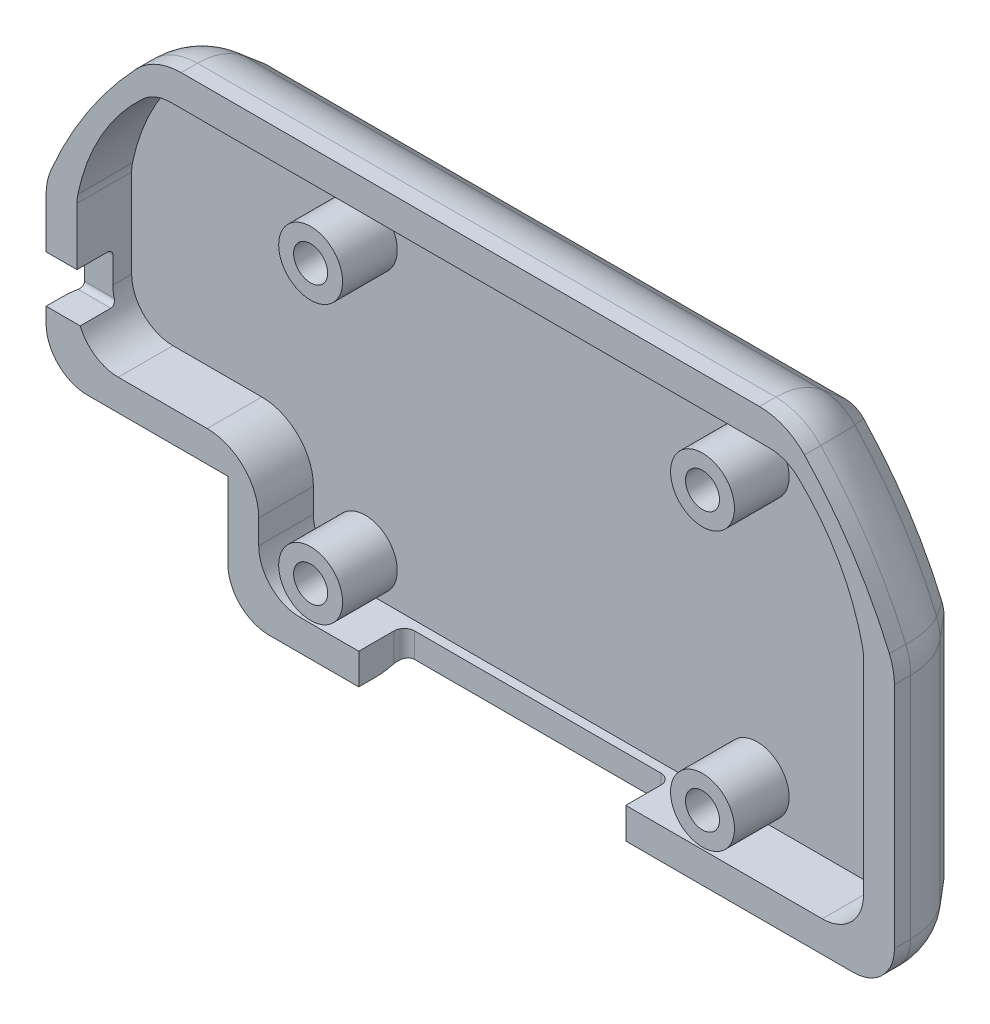
SolidWorks part; units mm, degrees
ref_plane "Alzado" through (0, 0, 0) normal (0, 0, 1) x (1, 0, 0)
ref_plane "Planta" through (0, 0, 0) normal (0, 1, 0) x (1, 0, 0)
ref_plane "Vista lateral" through (0, 0, 0) normal (1, 0, 0) x (0, 0, -1)
sketch "Croquis2" plane through (0, 0, 0) normal (0, 0, 1) x (1, 0, 0)
  line L0 (-43.6, 25.3285) -> (-43.6, 41.313)
  line L1 (-32.9688, 56.9561) -> (28.051, 56.9561)
  line L2 (38.6624, 41.313) -> (38.6624, 25.3285)
  line L7 (-43.6, 25.3285) -> (-25.98, 25.3285)
  line L8 (-25.98, 25.3285) -> (-25.98, 13.9787)
  line L9 (-25.98, 13.9787) -> (38.6624, 13.9787)
  line L10 (38.6624, 13.9787) -> (38.6624, 25.3285)
  arc A0 (-43.6, 41.313) -> (-32.9688, 56.9561) centre (-3.7394, 25.6575) cw
  arc A1 (28.051, 56.9561) -> (38.6624, 41.313) centre (-1.2097, 25.6867) cw
extrude "Saliente-Extruir1" add sketch "Croquis2" along normal blind 8.3
sketch "Croquis3" plane through (0, 0, 8.3) normal (0, 0, 1) x (1, 0, 0)
  line L0 (35.6624, 41.313) -> (35.6624, 28.3285)
  line L1 (-40.6, 28.3285) -> (-22.98, 28.3285)
  line L2 (-40.6, 41.313) -> (-40.6, 28.3285)
  line L7 (-22.98, 28.3285) -> (-22.98, 16.9787)
  line L8 (-22.98, 16.9787) -> (35.6624, 16.9787)
  line L11 (35.6624, 16.9787) -> (35.6624, 28.3285)
  line L17 (-32.9688, 53.9561) -> (28.0724, 53.9561)
  arc A0 (-40.6, 41.313) -> (-32.9688, 53.9561) centre (-19.994, 37.5001) cw
  arc A1 (28.0724, 53.9561) -> (35.6624, 41.313) centre (14.5103, 37.2147) cw
extrude "Cortar-Extruir1" cut sketch "Croquis3" against normal blind 5.3
fillet "Redondeo1" radius 4 10 edges at (35.6624, 16.9787, 5.65) (35.6624, 41.313, 5.65) (28.0724, 53.9561, 5.65) (-22.98, 16.9787, 5.65) (-40.6, 28.3285, 5.65) (-32.9688, 53.9561, 5.65) (-40.6, 41.313, 5.65) (38.6624, 13.9787, 4.15) (-25.98, 13.9787, 4.15) (-43.6, 25.3285, 4.15)
fillet "Redondeo2" radius 6 4 edges at (-43.6, 41.313, 4.15) (-32.9688, 56.9561, 4.15) (38.6624, 41.313, 4.15) (28.051, 56.9561, 4.15)
chamfer "Chaflán1" distance 3.5 angle 50 15 edges at (27.9535, 56.4654, 0) (-2.4607, 56.9561, 0) (-32.872, 56.4667, 0) (-39.5452, 49.1503, 0) (-43.478, 41.3361, 0) (-43.6, 34.7305, 0) (-42.4285, 26.5001, 0) (-32.79, 25.3285, 0) (-25.98, 21.6536, 0) (-24.8085, 15.1503, 0) (6.3412, 13.9787, 0) (37.4908, 15.1503, 0) (38.6624, 29.0568, 0) (38.5409, 41.3362, 0) (34.6182, 49.1458, 0) first distance on face at (-6.9571, 35.4937, 0)
fillet "Redondeo3" radius 7 15 edges at (-42.4285, 26.5001, 4.1711) (-24.8085, 15.1503, 4.1711) (-32.79, 25.3285, 4.1711) (-25.98, 21.6536, 4.1711) (-43.6, 34.7305, 4.1711) (-43.478, 41.3361, 4.1711) (-39.5452, 49.1503, 4.1711) (-32.872, 56.4667, 4.1711) (27.9535, 56.4654, 4.1711) (-2.4607, 56.9561, 4.1711) (38.5409, 41.3362, 4.1711) (34.6182, 49.1458, 4.1711) (38.6624, 29.0568, 4.1711) (37.4908, 15.1503, 4.1711) (6.3412, 13.9787, 4.1711)
sketch "Croquis4" plane through (0, 0, 0) normal (0, 0, -1) x (-1, 0, 0)
  circle A8 centre (-20.0535, 20.2867) radius 2.775
  circle A10 centre (-20.0535, 47.1867) radius 2.775
  circle A11 centre (17.9465, 47.2217) radius 2.775
  circle A12 centre (17.9465, 20.3217) radius 2.755
  dimension "D2" = 26.9
extrude "Cortar-Extruir2" cut sketch "Croquis4" against normal blind 5
sketch "Croquis7" plane through (-23.5317, 0, -19.7454) normal (-0.766, 0, -0.6428) x (-0.6428, 0, 0.766)
sketch "Croquis8" plane through (-43.6, 0, 0) normal (-1, 0, 0) x (0, 0, 1)
  line L0 (8.6236, 35.3575) -> (8.6236, 30.7915)
  line L4 (4.8292, 35.3575) -> (4.8292, 30.7915)
  line L5 (4.8292, 30.7915) -> (8.6236, 30.7915)
  line L6 (8.6236, 35.3575) -> (4.8292, 35.3575)
extrude "Cortar-Extruir3" cut sketch "Croquis8" against normal blind 5
sketch "Croquis9" plane through (-25.98, 0, 0) normal (-1, 0, 0) x (0, 0, 1)
  line L0 (8.4088, 23.1178) -> (8.4088, 17.9733)
  line L1 (8.4088, 23.1178) -> (4.7271, 23.1178)
  line L2 (4.7271, 23.1178) -> (4.7935, 18.0212)
  line L3 (4.7935, 18.0212) -> (8.4088, 17.9733)
fillet "Redondeo8" radius 5 1 edges at (-22.98, 28.3285, 5.65)
sketch "Croquis12" plane through (0, 0, 3) normal (0, 0, 1) x (1, 0, 0)
  circle A1 centre (-17.9465, 47.2217) radius 3.1
  circle A2 centre (-17.9465, 47.2217) radius 1.65
  circle A3 centre (-17.9465, 20.3217) radius 1.65
  circle A4 centre (-17.9465, 20.3217) radius 3.1
  circle A5 centre (20.0535, 20.2867) radius 1.65
  circle A6 centre (20.0535, 20.2867) radius 3.1
  circle A7 centre (20.0535, 47.1867) radius 1.65
  circle A8 centre (20.0535, 47.1867) radius 3.1
  circle A10 centre (20.0535, 20.2867) radius 2.775 construction
  circle A11 centre (20.0535, 47.1867) radius 2.775 construction
  circle A14 centre (-17.9465, 47.2217) radius 2.775 construction
  circle A15 centre (-17.9465, 20.3217) radius 2.755 construction
extrude "Saliente-Extruir4" add sketch "Croquis12" along normal up to surface (5.3 mm away) up to face at (-10.4031, 35.2913, 8.3)
fillet "Redondeo9" radius 0.5 2 edges at (-41.8165, 30.7915, 4.8292) (-41.9701, 35.3575, 4.8292)
sketch "Croquis14" plane through (0, 16.9787, 0) normal (0, 1, 0) x (1, 0, 0)
  line L1 (-13.279, -9.379) -> (-13.2784, -3.8865)
  line L2 (-13.2784, -3.8865) -> (12.6103, -3.8865)
  line L3 (12.6103, -3.8865) -> (12.6103, -11.0043)
  line L4 (12.6103, -11.0043) -> (-13.279, -9.379)
extrude "Cortar-Extruir4" cut sketch "Croquis14" against normal blind 10
fillet "Redondeo10" radius 1 2 edges at (-13.2784, 15.7781, 3.8865) (12.6103, 15.7781, 3.8865)
